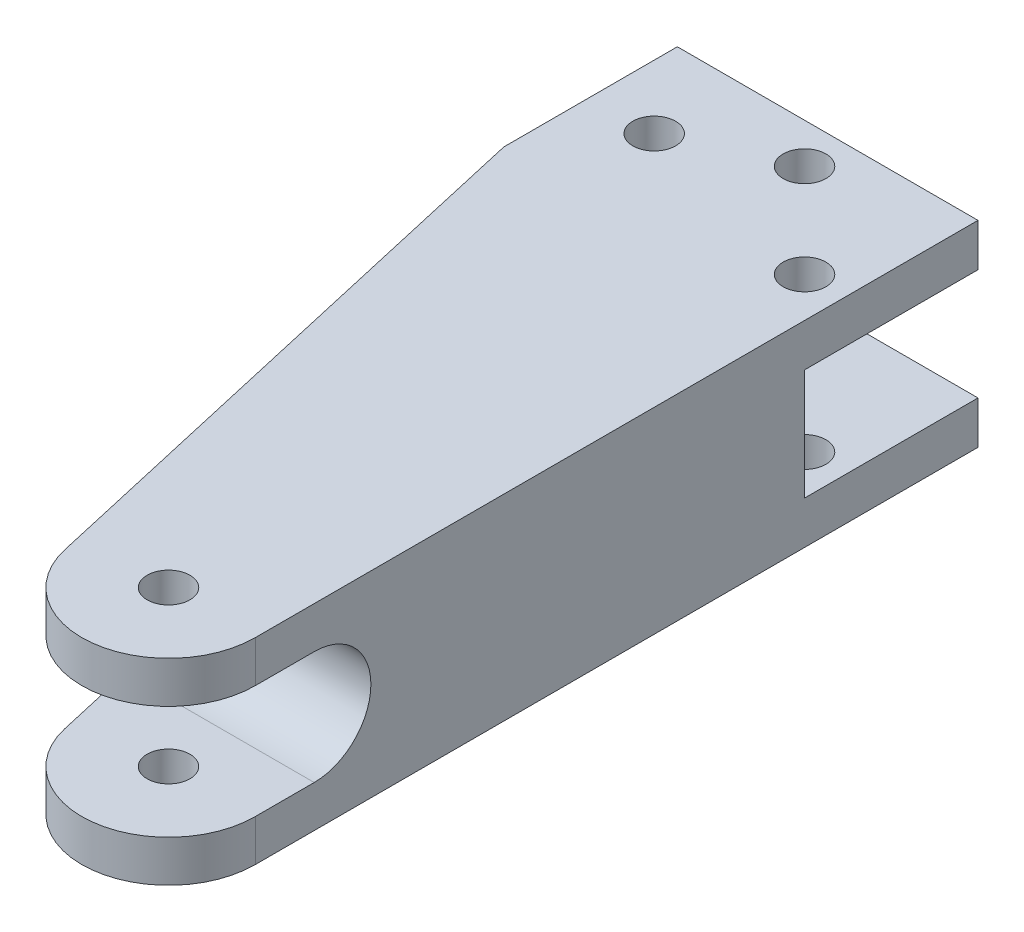
SolidWorks part; units mm, degrees
material "Cast Alloy Steel"
ref_plane "Front Plane" through (0, 0, 0) normal (0, 0, 1) x (1, 0, 0)
ref_plane "Top Plane" through (0, 0, 0) normal (0, 1, 0) x (1, 0, 0)
ref_plane "Right Plane" through (0, 0, 0) normal (1, 0, 0) x (0, 0, -1)
sketch "Sketch1" plane through (0, 0, 0) normal (0, 0, 1) x (1, 0, 0)
  line L0 (-9.525, -10.795) -> (9.525, -10.795)
  line L1 (-9.525, -10.795) -> (-9.525, 10.795)
  line L2 (9.525, -10.795) -> (9.525, 10.795)
  line L3 (-9.525, 10.795) -> (9.525, 10.795)
  line L4 (-9.525, -10.795) -> (9.525, 10.795) construction
  line L5 (9.525, -10.795) -> (-9.525, 10.795) construction
  point P1 (0, 0)
  dimension "D1" = 21.59
  dimension "D2" = 19.05
extrude "Boss-Extrude1" add sketch "Sketch1" along normal blind 88.9
sketch "Sketch3" plane through (0, 10.795, 0) normal (0, 1, 0) x (1, 0, 0)
  line L0 (-9.525, -88.9) -> (-9.525, 0) construction
  line L1 (9.525, -88.9) -> (9.525, 0) construction
  line L2 (9.525, -88.9) -> (-9.525, -88.9) construction
  arc A0 (-9.525, -79.375) -> (9.525, -79.375) centre (0, -79.375) ccw
extrude "Cut-Extrude-Thin1" cut sketch "Sketch3" against normal blind 88.9 and the other way through all thin thin type one direction wall 25.4
sketch "Sketch4" plane through (0, 10.795, 0) normal (0, 1, 0) x (1, 0, 0)
  line L0 (5.1435, -14.6685) -> (9.525, -14.6685) construction
  line L1 (9.525, -79.375) -> (9.525, 0) construction
  line L2 (-9.525, 0) -> (9.525, -19.05) construction
  line L3 (-5.1435, -4.3815) -> (-5.1435, 0) construction
  line L4 (-9.525, 0) -> (9.525, 0) construction
  line L5 (-9.525, 0) -> (-9.525, -19.05) construction
  line L6 (-9.525, -19.05) -> (9.525, -19.05) construction
  line L7 (9.525, 0) -> (9.525, -19.05) construction
  circle A0 centre (0, -79.375) radius 2.3495
  circle A1 centre (5.1435, -14.6685) radius 2.3495
  circle A2 centre (-5.1435, -4.3815) radius 2.3495
  dimension "D1" = 4.699
  dimension "D2" = 4.3815
  dimension "D3" = 4.3815
extrude "Cut-Extrude1" cut sketch "Sketch4" against normal through all
sketch "Sketch5" plane through (0, 10.795, 0) normal (0, 1, 0) x (1, 0, 0)
  line L0 (-9.525, 0) -> (-23.495, 0)
  line L1 (-23.495, 0) -> (-23.495, -19.05)
  line L2 (-9.525, -79.375) -> (-9.525, 0) construction
  line L3 (-9.525, -79.375) -> (-9.525, 0)
  line L4 (-23.495, -19.05) -> (-9.2876, -81.4883)
  arc A0 (-9.525, -79.375) -> (9.525, -79.375) centre (0, -79.375) ccw construction
  arc A1 (-9.525, -79.375) -> (9.525, -79.375) centre (0, -79.375) ccw
  circle A2 centre (-16.51, -9.525) radius 2.3495
  circle A3 centre (-5.1435, -4.3815) radius 2.3495 construction
  point P14 (-16.51, 0)
  point P17 (-23.495, -9.525)
  line M9 (-9.525, 0) -> (-9.525, -79.375)
  arc M10 (-9.525, -79.375) -> (9.525, -79.375) centre (0, -79.375) ccw
  dimension "D1" = 13.97
  dimension "D2" = 19.05
  dimension "D3" = 12.819
extrude "Boss-Extrude2" add sketch "Sketch5" against normal up to surface (21.59 mm away) contours L1 L4 L0 A2 M10 M9 region at (-15.0361, 10.795, 28.5077) up to face at (0, -10.795, 81.7245)
sketch "Sketch6" plane through (9.525, 0, 0) normal (1, 0, 0) x (0, 0, -1)
  line L0 (19.05, -6.096) -> (19.05, 6.096)
  line L1 (19.05, -6.096) -> (-19.05, -6.096)
  line L2 (19.05, 6.096) -> (-19.05, 6.096)
  line L3 (-19.05, -6.096) -> (-19.05, 6.096)
  line L4 (19.05, -6.096) -> (-19.05, 6.096) construction
  line L5 (19.05, 6.096) -> (-19.05, -6.096) construction
  line L6 (-92.075, -6.223) -> (-72.898, -6.223)
  line L7 (-92.075, -6.223) -> (-92.075, 6.223)
  line L9 (-92.075, 6.223) -> (-72.898, 6.223)
  line L10 (-92.075, -6.223) -> (-69.1843, 4.9934) construction
  line L11 (-69.1843, -4.9934) -> (-92.075, 6.223) construction
  line L12 (-79.375, -10.795) -> (-79.375, 10.795) construction
  line L13 (-79.375, -10.795) -> (-79.375, 10.795) construction
  arc A0 (-72.898, 6.223) -> (-72.898, -6.223) centre (-72.898, 0) cw
  point P1 (0, 0)
  point P2 (-79.375, 0)
  point P14 (-79.375, 0)
  dimension "D1" = 12.192
  dimension "D2" = 19.05
extrude "Cut-Extrude2" cut sketch "Sketch6" against normal through all
